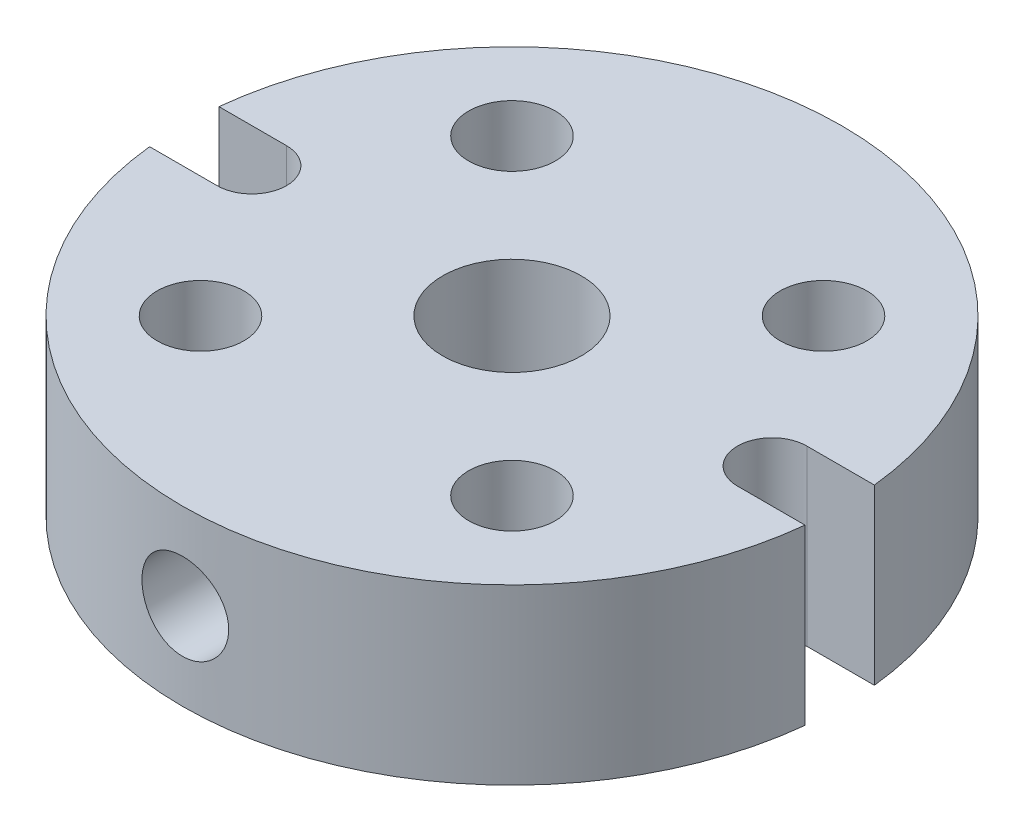
SolidWorks part; units mm, degrees
ref_plane "Front Plane" through (0, 0, 0) normal (0, 0, 1) x (1, 0, 0)
ref_plane "Top Plane" through (0, 0, 0) normal (0, 1, 0) x (1, 0, 0)
ref_plane "Right Plane" through (0, 0, 0) normal (1, 0, 0) x (0, 0, -1)
sketch "Sketch1" plane through (0, 0, 0) normal (0, 1, 0) x (1, 0, 0)
  line L0 (-9.5, 0) -> (9.5, 0) construction
  line L1 (0, 9.5) -> (0, -9.5) construction
  line L2 (0, 0) -> (6.7175, 6.7175) construction
  circle A0 centre (0, 0) radius 9.5
  circle A1 centre (0, 0) radius 2
  circle A2 centre (4.4901, 4.4901) radius 1.25
  circle A3 centre (-4.4901, 4.4901) radius 1.25
  circle A4 centre (4.4901, -4.4901) radius 1.25
  circle A5 centre (-4.4901, -4.4901) radius 1.25
  dimension "D1" = 19
  dimension "D2" = 4
  dimension "D3" = 2.5
  dimension "D4" = 6.35
  dimension "D5" = 45
extrude "Base shape" add sketch "Sketch1" along normal blind 5
ref_plane "Plane2" through (0, 0, 9.5) normal (0, 0, 1) x (1, 0, 0)
sketch "Sketch3" plane through (0, 0, 9.5) normal (0, 0, 1) x (1, 0, 0)
  line L0 (-9.5, 2.5) -> (9.5, 2.5) construction
  line L1 (-9.5, 5) -> (-9.5, 0) construction
  line L2 (9.5, 0) -> (9.5, 5) construction
  circle A0 centre (0, 2.5) radius 1.25
  dimension "D1" = 2.5
extrude "Grub screw cut" cut sketch "Sketch3" against normal up to next
sketch "Sketch4" plane through (0, 5, 0) normal (0, 1, 0) x (1, 0, 0)
  line L0 (-9.5, 0) -> (9.5, 0) construction
  line L1 (-9.4472, 0) -> (-7.5, 0) construction
  line L2 (-9.4472, 1) -> (-7.5, 1)
  line L3 (-9.4472, -1) -> (-7.5, -1)
  line L4 (0, 9.5) -> (0, -9.5) construction
  line L5 (9.4472, 0) -> (7.5, 0) construction
  line L6 (9.4472, 1) -> (7.5, 1)
  line L7 (9.4472, -1) -> (7.5, -1)
  circle A0 centre (0, 0) radius 9.5 construction
  arc A1 (-9.4472, 1) -> (-9.4472, -1) centre (-9.4472, 0) ccw
  arc A2 (-7.5, -1) -> (-7.5, 1) centre (-7.5, 0) ccw
  arc A3 (9.4472, 1) -> (9.4472, -1) centre (9.4472, 0) cw
  arc A4 (7.5, -1) -> (7.5, 1) centre (7.5, 0) cw
  point P7 (-8.4736, 0)
  point P14 (-10.0602, 0)
  point P15 (0, 0)
  point P18 (8.4736, 0)
  dimension "D1" = 15
  dimension "D2" = 2
extrude "Motor screw slots" cut sketch "Sketch4" against normal up to next
